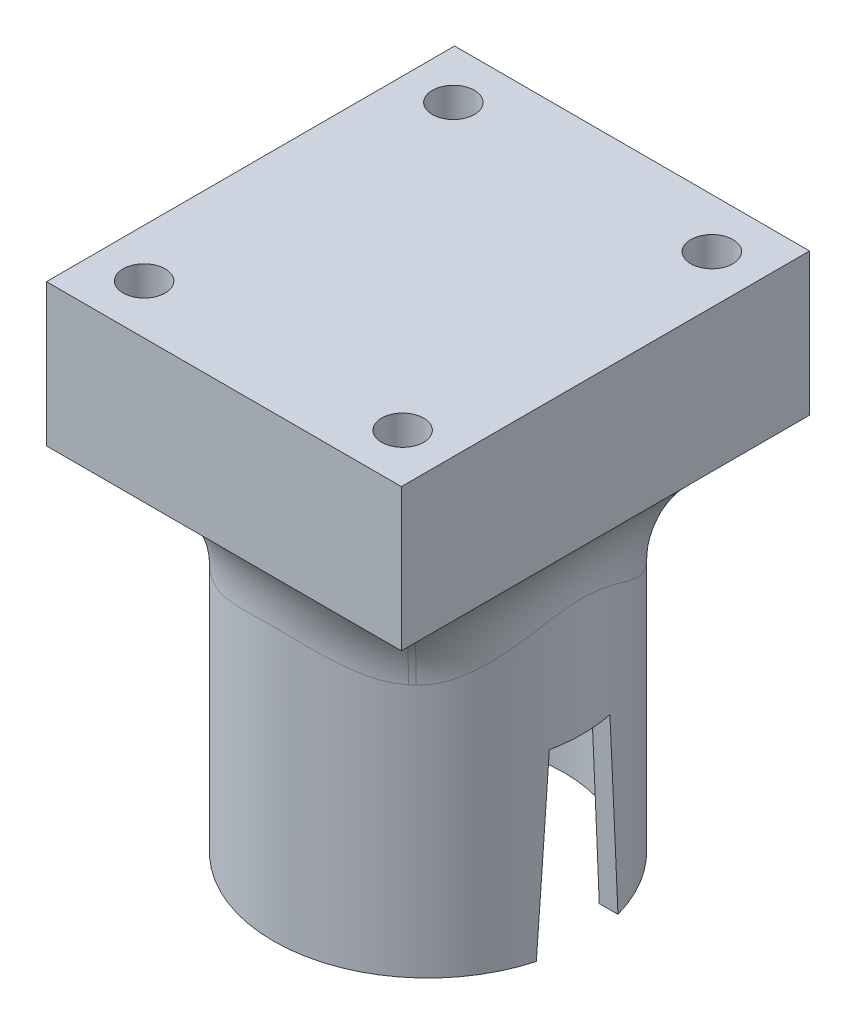
SolidWorks part; units mm, degrees
ref_plane "Front Plane" through (0, 0, 0) normal (0, 0, 1) x (1, 0, 0)
ref_plane "Top Plane" through (0, 0, 0) normal (0, 1, 0) x (1, 0, 0)
ref_plane "Right Plane" through (0, 0, 0) normal (1, 0, 0) x (0, 0, -1)
sketch "Sketch1" plane through (0, 0, 0) normal (0, 1, 0) x (1, 0, 0)
  circle A0 centre (0, 0) radius 12.5
  circle A1 centre (0, 0) radius 11.05
  dimension "D1" = 22.1
  dimension "D2" = 25
extrude "Boss-Extrude1" add sketch "Sketch1" along normal blind 14.5
sketch "Sketch2" plane through (0, 0, 0) normal (1, 0, 0) x (0, 0, -1)
  line L0 (0, 0) -> (0, 21.5035) construction
  line L1 (12.5, 14.5) -> (0, 14.5)
  line L2 (12.5, 14.5) -> (12.5, 29.5)
  line L3 (12.5, 29.5) -> (0, 29.5)
  line L4 (11.05, 14.5) -> (-11.05, 14.5) construction
  line L5 (0, 29.5) -> (0, 14.5)
  line L6 (12.5, 0) -> (12.5, 14.5) construction
  dimension "D1" = 15
revolve "Revolve1" add sketch "Sketch2" angle 360 about L0
sketch "Sketch3" plane through (0, 29.5, 0) normal (0, 1, 0) x (1, 0, 0)
  line L1 (14.35, -16.5) -> (-14.35, -16.5)
  line L2 (14.35, -16.5) -> (14.35, 16.5)
  line L3 (14.35, 16.5) -> (-14.35, 16.5)
  line L4 (-14.35, -16.5) -> (-14.35, 16.5)
  line L5 (14.35, -16.5) -> (-14.35, 16.5) construction
  line L6 (14.35, 16.5) -> (-14.35, -16.5) construction
  point P0 (0, 0)
  dimension "D1" = 28.7
  dimension "D2" = 33
extrude "Boss-Extrude2" add sketch "Sketch3" along normal blind 11.5
fillet "Fillet1" radius 9 1 edges at (0, 29.5, -12.5)
hole_wizard "Ø3.0mm Dowel Hole1" positions "Sketch4" profile "Sketch5" hole size "Ø3.0" standard "ANSI Metric"
sketch "Sketch4" plane through (0, 41, 0) normal (0, 1, 0) x (1, 0, 0)
  line L0 (-10.45, -12.5) -> (-10.45, 12.5) construction
  line L1 (-10.45, 12.5) -> (10.45, 12.5) construction
  line L2 (10.45, 12.5) -> (10.45, -12.5) construction
  line L3 (10.45, -12.5) -> (-10.45, -12.5) construction
  line L5 (-10.45, 12.5) -> (10.45, -12.5) construction
  point P0 (-10.45, 12.5)
  point P2 (10.45, 12.5)
  point P4 (10.45, -12.5)
  point P6 (-10.45, -12.5)
  point P22 (0, 0)
  dimension "D1" = 20.9
  dimension "D2" = 25
sketch "Sketch5" plane through (-10.45, 41, -12.5) normal (1, 0, 0) x (0, 0, 1)
  line L0 (0, 0) -> (0, 10.0215)
  line L1 (0, 10.0215) -> (1.7, 9)
  line L2 (1.7, 9) -> (1.7, 0)
  line L5 (1.7, 0) -> (0, 0)
  line L10 (0, 10.0215) -> (-1.7, 9) construction
  line L11 (0, -6.35) -> (0, 107.95) construction
  dimension "Hole Dia." = 3.4
  dimension "Hole Depth" = 9
  dimension "Drill Angle" = 118
sketch "Sketch6" plane through (0, 41, 0) normal (0, 1, 0) x (1, 0, 0)
  circle A0 centre (-10.45, 12.5) radius 3.1
  circle A1 centre (10.45, 12.5) radius 3.1
  circle A2 centre (10.45, -12.5) radius 3.1
  circle A3 centre (-10.45, -12.5) radius 3.1
  dimension "D1" = 6.2
extrude "Cut-Extrude1" cut sketch "Sketch6" against normal blind 2.8 from offset 3 offset against normal yes
sketch "Sketch7" plane through (-14.35, 0, 0) normal (-1, 0, 0) x (0, 0, 1)
  line L0 (0, 0) -> (0, 24.034) construction
  line L1 (-3.3, 0) -> (3.3, 0)
  line L2 (-12.5, 0) -> (12.5, 0) construction
  line L3 (3.3, 0) -> (2.45, 14.5)
  line L4 (2.45, 14.5) -> (-2.45, 14.5)
  line L5 (-2.45, 14.5) -> (-3.3, 0)
  spline S0 degree 3 poles (9.3083, 20.5) (8.9925, 20.5) (8.6664, 20.5599) (8.161, 20.7076) (7.9898, 20.7667) (7.6418, 20.9011) (7.4642, 20.9768) (6.5735, 21.383) (5.852, 21.7923) (4.7219, 22.4214) (4.3373, 22.6342) (3.5426, 23.0469) (3.1376, 23.2442) (2.3038, 23.5931) (1.8748, 23.745) (1.2019, 23.9101) (0.9709, 23.9547) (0.5045, 24.0159) (0.0381, 24.0486) (-0.4284, 24.0223) (-0.8949, 23.9673) (-1.1276, 23.9253) (-1.8097, 23.7657) (-2.2522, 23.6126) (-3.1019, 23.2611) (-3.5088, 23.0636) (-4.3017, 22.6535) (-4.6874, 22.4405) (-5.8261, 21.8069) (-6.566, 21.3875) (-7.626, 20.9025) (-7.9724, 20.7639) (-8.4841, 20.6127) (-8.6543, 20.5716) (-8.9874, 20.5153) (-9.1499, 20.5) (-9.3083, 20.5) knots 0 0 0 0 0.0625 0.0625 0.09375 0.09375 0.125 0.125 0.25 0.25 0.3125 0.3125 0.375 0.375 0.4375 0.4375 0.46875 0.46875 0.5 0.53125 0.53125 0.5625 0.5625 0.625 0.625 0.6875 0.6875 0.75 0.75 0.875 0.875 0.9375 0.9375 0.96875 0.96875 1 1 1 1 construction
  dimension "D1" = 4.9
  dimension "D2" = 6.6
  dimension "D3" = 14.5
extrude "Cut-Extrude2" cut sketch "Sketch7" against normal through all
